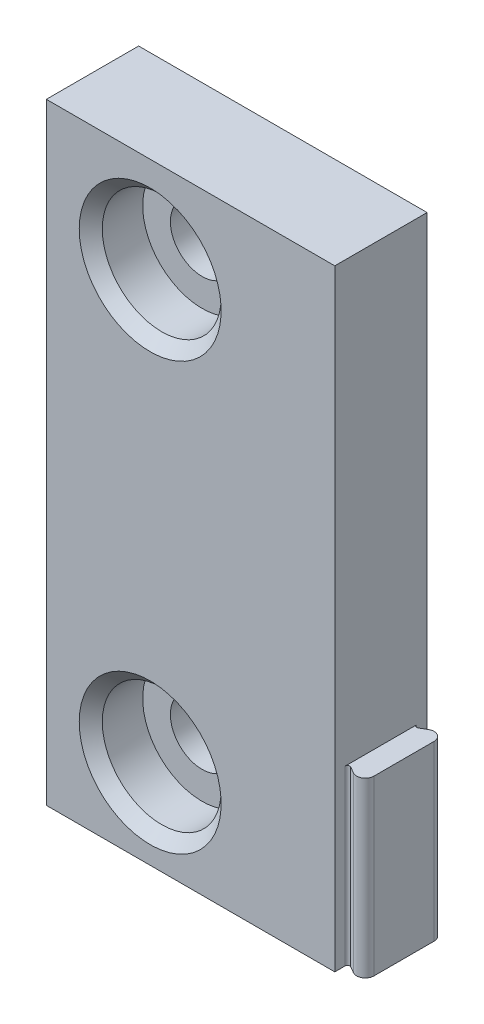
SolidWorks part; units mm, degrees
ref_plane "Front Plane" through (0, 0, 0) normal (0, 0, 1) x (1, 0, 0)
ref_plane "Top Plane" through (0, 0, 0) normal (0, 1, 0) x (1, 0, 0)
ref_plane "Right Plane" through (0, 0, 0) normal (1, 0, 0) x (0, 0, -1)
sketch "Sketch2" plane through (0, 0, 0) normal (0, 0, 1) x (1, 0, 0)
  line L1 (0, 0) -> (25, 0)
  line L2 (0, 0) -> (0, 53)
  line L3 (0, 53) -> (25, 53)
  line L4 (25, 0) -> (25, 53)
  line L5 (0, 26.2) -> (42.3407, 26.2) construction
  circle A0 centre (9, 44.7) radius 2.75
  circle A1 centre (9, 7.7) radius 2.75
  point P9 (8.4768, 44.7)
  point P10 (0, 0)
  dimension "D3" = 5.5
  dimension "D1" = 53
  dimension "D2" = 25
  dimension "D4" = 18.5
  dimension "D5" = 18.5
  dimension "D6" = 26.2
  dimension "D7" = 9
extrude "Boss-Extrude1" add sketch "Sketch2" along normal blind 8
sketch "Sketch3" plane through (0, 0, 0) normal (0, -1, 0) x (1, 0, 0)
  line L0 (25, 1.25) -> (27, 0.0953)
  line L1 (27, 0.0953) -> (27, 7.9047)
  line L2 (27, 7.9047) -> (25, 6.75)
  line L3 (25, 8) -> (25, 0) construction
  line L4 (25, 1.25) -> (25, 6.75)
  point P11 (25, 4)
  point P12 (25, 4)
  dimension "D1" = 60
  dimension "D2" = 60
  dimension "D3" = 2
  dimension "D4" = 5.5
extrude "Boss-Extrude2" add sketch "Sketch3" against normal blind 15
sketch "Sketch4" plane through (0, 0, 8) normal (0, 0, 1) x (1, 0, 0)
  circle A0 centre (9, 44.7) radius 5.15
  circle A1 centre (9, 7.7) radius 5.15
  dimension "D1" = 10.3
extrude "Cut-Extrude1" cut sketch "Sketch4" against normal blind 4.5
chamfer "Chamfer1" distance 1 angle 45 2 edges at (14.15, 44.7, 8) (14.15, 7.7, 8)
fillet "Fillet1" radius 0.75 2 edges at (27, 7.5, 0.0953) (27, 7.5, 7.9047)
fillet "Fillet3" radius 0.2 2 edges at (25, 7.5, 6.75) (25, 7.5, 1.25)
equation "\"D5@Sketch2\"=(11+25)/2 +.5"
equation "\"D4@Sketch2\"=\"D5@Sketch2\""
